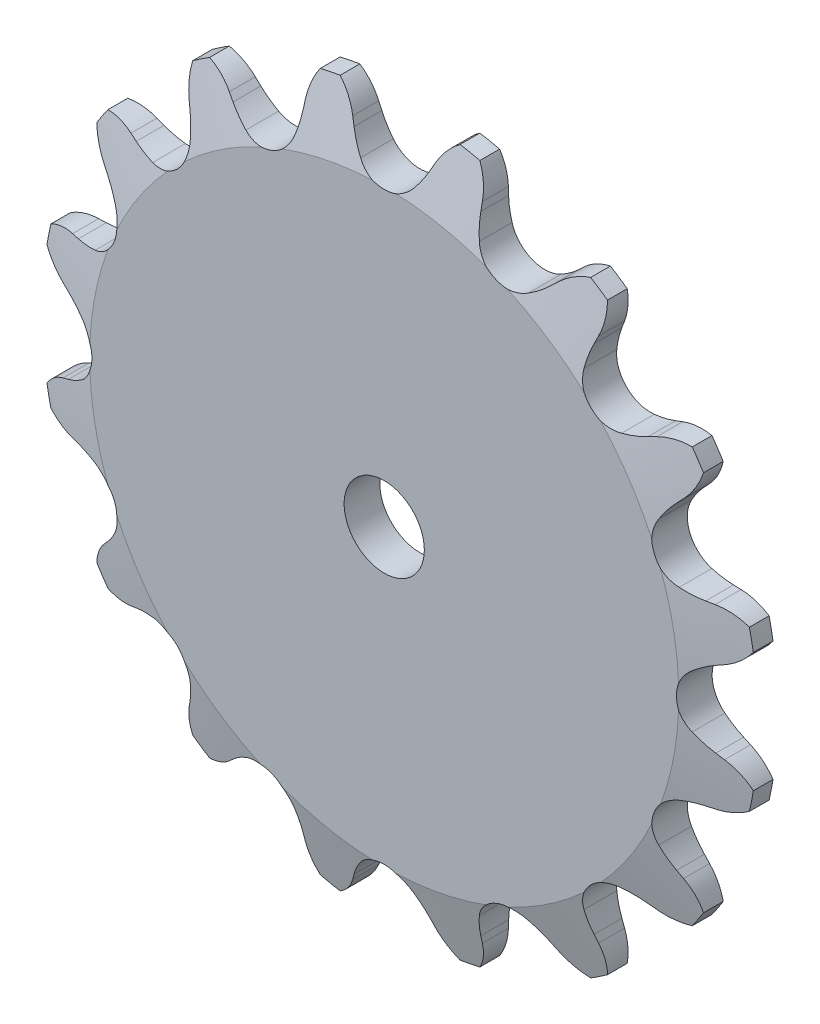
SolidWorks part; units mm, degrees
ref_plane "Front Plane" through (0, 0, 0) normal (0, 0, 1) x (1, 0, 0)
ref_plane "Top Plane" through (0, 0, 0) normal (0, 1, 0) x (1, 0, 0)
ref_plane "Right Plane" through (0, 0, 0) normal (1, 0, 0) x (0, 0, -1)
ref_axis "Axis1" through (0, 0, -88.99) along (0, 0, 1)
sketch "Sprocket-BaseSketch" plane through (0, 0, 0) normal (1, 0, 0) x (0, 0, -1)
  line L0 (1.397, 0) -> (1.397, 14.6918)
  line L1 (1.397, 14.6918) -> (0.6032, 17.8668)
  line L2 (0.6032, 17.8668) -> (-0.6032, 17.8668)
  line L3 (-0.6032, 17.8668) -> (-1.397, 14.6918)
  line L4 (-1.397, 14.6918) -> (-1.397, 0)
  line L5 (-1.397, 0) -> (1.397, 0)
  line L6 (5.588, 0) -> (-1.7463, 0) construction
  dimension "Hub Surface" = 1.397
  dimension "RightSide (1)" = 0.7938
  dimension "RightSide (2)" = 3.175
  dimension "OD" = 17.8668
  dimension "LeftSide (1)" = 0.7938
  dimension "LeftSide (2)" = 3.175
  dimension "Tooth Width" = 2.794
revolve "25 (04C) ANSI (ISO) Chain Number, 1.281in P.D." add sketch "Sprocket-BaseSketch" angle 360 about L6
sketch "Tooth-Sketch" plane through (0, 0, 0) normal (0, 0, 1) x (1, 0, 0)
  line L0 (0, 0) -> (0, 21.6994) construction
  line L1 (1.896, 16.1459) -> (2.0514, 16.491)
  line L2 (-1.896, 16.1459) -> (-2.0514, 16.491)
  line L3 (0, 16.2745) -> (6.228, 15.0357) construction
  line L4 (0, 16.2745) -> (-6.228, 15.0357) construction
  arc A0 (-1.3237, 15.2121) -> (1.3237, 15.2121) centre (0, 16.2745) ccw
  arc A1 (1.3237, 15.2121) -> (1.896, 16.1459) centre (-2.0601, 17.928) ccw
  arc A2 (-1.3237, 15.2121) -> (-1.896, 16.1459) centre (2.0601, 17.928) cw
  arc A3 (2.0514, 16.491) -> (4.534, 18.0955) centre (4.534, 15.3726) cw
  arc A4 (-2.0514, 16.491) -> (-4.534, 18.0955) centre (-4.534, 15.3726) ccw
  arc A5 (4.534, 18.0955) -> (-4.534, 18.0955) centre (0, 0) ccw
extrude "Tooth-Cut, Number of teeth: 16" cut sketch "Tooth-Sketch" against normal through all and the other way through all
pattern_circular "Tooth Pattern, 16 / 16" count 16 every 22.5 about axis through (0, 0, -88.99) along (0, 0, 1) of "Tooth-Cut, Number of teeth: 16"
sketch "Sketch4" plane through (0, 0, 0) normal (0, 0, 1) x (1, 0, 0)
  circle A0 centre (0, 0) radius 2
  dimension "D1" = 4
extrude "Cut-Extrude1" cut sketch "Sketch4" against normal through all and the other way through all
sketch "Sketch5" plane through (0, 0, 0) normal (0, 0, 1) x (1, 0, 0)
  circle A0 centre (0, 0) radius 17.8668 construction
  dimension "D1" = 35.7336
sketch "Sketch6" plane through (0, 0, -1.397) normal (0, 0, -1) x (-1, 0, 0)
  circle A0 centre (0, 0) radius 27.1758
extrude "Cut-Extrude2" cut sketch "Sketch6" against normal blind 1.016
equation "\"D1@Sketch5\" = \"OD@Sprocket-BaseSketch\"*2"
